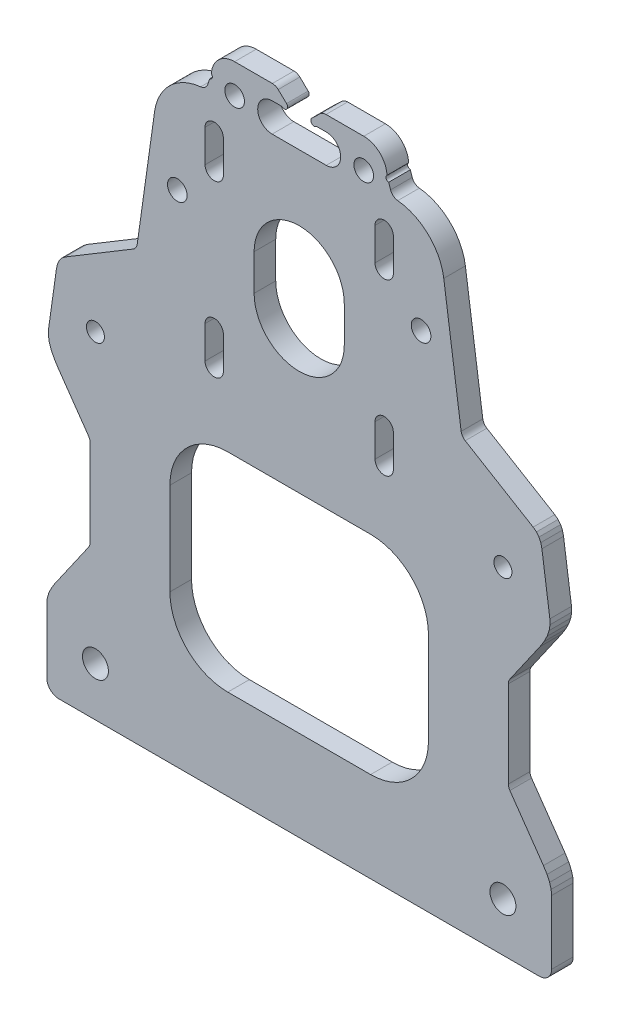
SolidWorks part; units mm, degrees
ref_plane "Front" through (0, 0, 0) normal (0, 0, 1) x (1, 0, 0)
ref_plane "Top" through (0, 0, 0) normal (0, 1, 0) x (1, 0, 0)
ref_plane "Right" through (0, 0, 0) normal (1, 0, 0) x (0, 0, -1)
sketch "Model" plane through (0, 0, 0) normal (0, 0, 1) x (1, 0, 0)
  line L0 (-66.6404, 0) -> (66.6403, 0)
  line L1 (-69.9997, 21.1105) -> (-69.9997, 3.3593)
  line L2 (-69.5175, 87.3083) -> (-67.3079, 103.0302)
  line L3 (-67.3079, 103.0302) -> (-66.9899, 104.3736)
  line L4 (-66.9899, 104.3736) -> (-66.4641, 105.4734)
  line L5 (-66.4641, 105.4734) -> (-65.7645, 106.3363)
  line L6 (-65.7645, 106.3363) -> (-64.8747, 107.0176)
  line L7 (-69.9997, 21.1105) -> (-69.8655, 22.4981)
  line L8 (-69.8655, 22.4981) -> (-69.4453, 23.9884)
  line L9 (-69.4453, 23.9884) -> (-68.7321, 25.549)
  line L10 (-68.7321, 25.549) -> (-67.7328, 27.1616)
  line L11 (3.5003, 174.5536) -> (5.8203, 176.7548)
  line L12 (-19.8029, 25.0481) -> (19.8036, 25.0481)
  line L13 (-58.4275, 67.2803) -> (-66.7857, 79.2679)
  line L14 (-66.7857, 79.2679) -> (-67.9147, 81.0492)
  line L15 (-67.9147, 81.0492) -> (-68.7631, 82.7614)
  line L16 (-68.7631, 82.7614) -> (-69.3163, 84.3925)
  line L17 (-69.3163, 84.3925) -> (-69.5643, 85.9155)
  line L18 (-69.5643, 85.9155) -> (-69.5175, 87.3083)
  line L19 (-58.0053, 41.8651) -> (-58.0053, 65.9363)
  line L20 (-44.9176, 120.0252) -> (-40.0933, 154.3521)
  line L21 (-25.3495, 168.249) -> (-24.8281, 169.8174)
  line L22 (-64.8747, 107.0176) -> (-46.0344, 118.338)
  line L23 (-35.8497, 66.7013) -> (-35.8497, 41.0949)
  line L24 (-26.1097, 157.54) -> (-26.1097, 148.54)
  line L25 (-26.1097, 110.4) -> (-26.1097, 101.4)
  line L26 (-21.0297, 101.4) -> (-21.0297, 110.4)
  line L27 (-21.0297, 148.54) -> (-21.0297, 157.54)
  line L28 (-67.7328, 27.1616) -> (-58.4269, 40.5219)
  line L29 (-12.4997, 134.47) -> (-12.4997, 124.47)
  line L30 (19.8036, 82.7481) -> (-19.8029, 82.7481)
  line L31 (12.5003, 124.47) -> (12.5003, 134.47)
  line L32 (21.0304, 157.54) -> (21.0304, 148.54)
  line L33 (21.0304, 110.4) -> (21.0304, 101.4)
  line L34 (58.4317, 40.5252) -> (67.7348, 27.1616)
  line L35 (26.1103, 101.4) -> (26.1103, 110.4)
  line L36 (26.1103, 148.54) -> (26.1103, 157.54)
  line L37 (35.8504, 41.0949) -> (35.8504, 66.7013)
  line L38 (46.0351, 118.338) -> (64.8754, 107.0176)
  line L39 (24.8288, 169.8174) -> (25.3502, 168.249)
  line L40 (40.094, 154.3521) -> (44.9183, 120.0252)
  line L41 (58.0103, 65.9397) -> (58.0103, 41.8678)
  line L42 (66.7838, 79.2679) -> (58.4323, 67.2832)
  line L43 (64.8754, 107.0176) -> (65.7822, 106.3199)
  line L44 (65.7822, 106.3199) -> (66.4875, 105.4379)
  line L45 (66.4875, 105.4379) -> (66.9996, 104.3501)
  line L46 (66.9996, 104.3501) -> (67.3095, 103.0302)
  line L47 (-5.8196, 176.7548) -> (-3.4996, 174.5536)
  line L48 (70.0003, 21.1105) -> (69.8663, 22.4981)
  line L49 (69.8663, 22.4981) -> (69.4463, 23.9884)
  line L50 (69.4463, 23.9884) -> (68.7335, 25.5489)
  line L51 (68.7335, 25.5489) -> (67.7348, 27.1616)
  line L52 (67.3095, 103.0302) -> (69.5191, 87.3083)
  line L53 (69.5191, 87.3083) -> (69.5654, 85.916)
  line L54 (69.5654, 85.916) -> (69.3167, 84.3947)
  line L55 (69.3167, 84.3947) -> (68.7632, 82.7647)
  line L56 (68.7632, 82.7647) -> (67.9141, 81.0517)
  line L57 (67.9141, 81.0517) -> (66.7838, 79.2679)
  line L58 (70.0003, 3.36) -> (70.0003, 21.1105)
  line L59 (-7.4996, 165.2073) -> (7.5003, 165.2073)
  line L60 (7.5003, 173.2073) -> (4.8467, 173.2073)
  line L61 (-4.846, 173.2073) -> (-7.4996, 173.2073)
  line L62 (17.9111, 177.4) -> (7.4378, 177.4)
  line L63 (-7.4371, 177.4) -> (-17.9104, 177.4)
  arc A0 (-19.8029, 82.7481) -> (-35.8497, 66.7013) centre (-19.8028, 66.7013) ccw
  arc A1 (-35.8497, 41.0949) -> (-19.8029, 25.0481) centre (-19.8029, 41.0949) ccw
  circle A2 centre (-56.4996, 13.52) radius 3.6
  arc A3 (-69.9997, 3.3593) -> (-66.6404, 0) centre (-66.6403, 3.3593) ccw
  arc A4 (-58.0053, 65.9363) -> (-58.4275, 67.2803) centre (-60.3552, 65.9363) ccw
  arc A5 (-58.4269, 40.5219) -> (-58.0053, 41.8651) centre (-60.3553, 41.8651) ccw
  arc A6 (-27.3372, 166.653) -> (-40.0933, 154.3521) centre (-25.8547, 152.351) ccw
  arc A7 (-17.9104, 177.4) -> (-24.3548, 171.2408) centre (-17.9104, 170.949) ccw
  arc A8 (-7.4996, 173.2073) -> (-7.4996, 165.2073) centre (-7.4996, 169.2073) ccw
  circle A9 centre (-17.8997, 169.2073) radius 2.725
  circle A10 centre (-33.7996, 138.65) radius 2.725
  arc A11 (-21.0297, 157.54) -> (-26.1097, 157.54) centre (-23.5696, 157.54) ccw
  arc A12 (-26.1097, 148.54) -> (-21.0297, 148.54) centre (-23.5696, 148.54) ccw
  arc A13 (-21.0297, 110.4) -> (-26.1097, 110.4) centre (-23.5696, 110.4) ccw
  arc A14 (-26.1097, 101.4) -> (-21.0297, 101.4) centre (-23.5696, 101.4) ccw
  circle A15 centre (-56.4996, 93.22) radius 2.5
  arc A16 (-46.0344, 118.338) -> (-44.9176, 120.0252) centre (-47.2448, 120.3523) ccw
  arc A17 (-27.3372, 166.653) -> (-25.3495, 168.249) centre (-27.5795, 168.9904) ccw
  arc A18 (-5.8196, 176.7548) -> (-7.4371, 177.4) centre (-7.4371, 175.05) ccw
  arc A19 (-4.846, 173.2073) -> (-3.4996, 174.5536) centre (-4.1728, 173.8805) ccw
  arc A20 (-24.8281, 169.8174) -> (-24.3548, 171.2408) centre (-24.888, 170.6277) ccw
  arc A21 (19.8036, 25.0481) -> (35.8504, 41.0949) centre (19.8036, 41.0949) ccw
  arc A22 (35.8504, 66.7013) -> (19.8036, 82.7481) centre (19.8036, 66.7013) ccw
  circle A23 centre (56.5004, 13.52) radius 3.6
  arc A24 (66.6403, 0) -> (70.0003, 3.36) centre (66.6403, 3.36) ccw
  arc A25 (58.4323, 67.2832) -> (58.0103, 65.9397) centre (60.3603, 65.9397) ccw
  arc A26 (58.0103, 41.8678) -> (58.4317, 40.5252) centre (60.3603, 41.8678) ccw
  arc A27 (40.094, 154.3521) -> (27.3379, 166.653) centre (25.8554, 152.351) ccw
  arc A28 (12.5003, 134.47) -> (-12.4997, 134.47) centre (0.0004, 134.47) ccw
  arc A29 (-12.4997, 124.47) -> (12.5003, 124.47) centre (0.0004, 124.47) ccw
  arc A30 (24.3555, 171.2408) -> (17.9111, 177.4) centre (17.9111, 170.949) ccw
  arc A31 (7.5003, 165.2073) -> (7.5003, 173.2073) centre (7.5003, 169.2073) ccw
  circle A32 centre (17.9004, 169.2073) radius 2.725
  circle A33 centre (33.8004, 138.65) radius 2.725
  arc A34 (26.1103, 157.54) -> (21.0304, 157.54) centre (23.5703, 157.54) ccw
  arc A35 (21.0304, 148.54) -> (26.1103, 148.54) centre (23.5703, 148.54) ccw
  arc A36 (26.1103, 110.4) -> (21.0304, 110.4) centre (23.5703, 110.4) ccw
  arc A37 (21.0304, 101.4) -> (26.1103, 101.4) centre (23.5703, 101.4) ccw
  circle A38 centre (56.5004, 93.22) radius 2.5
  arc A39 (44.9183, 120.0252) -> (46.0351, 118.338) centre (47.2455, 120.3523) ccw
  arc A40 (25.3502, 168.249) -> (27.3379, 166.653) centre (27.5802, 168.9904) ccw
  arc A41 (7.4378, 177.4) -> (5.8203, 176.7548) centre (7.4378, 175.05) ccw
  arc A42 (3.5003, 174.5536) -> (4.8467, 173.2073) centre (4.1735, 173.8805) ccw
  arc A43 (24.3555, 171.2408) -> (24.8288, 169.8174) centre (24.8887, 170.6277) ccw
extrude "Boss-Extrude1" add sketch "Model" along normal blind 6
